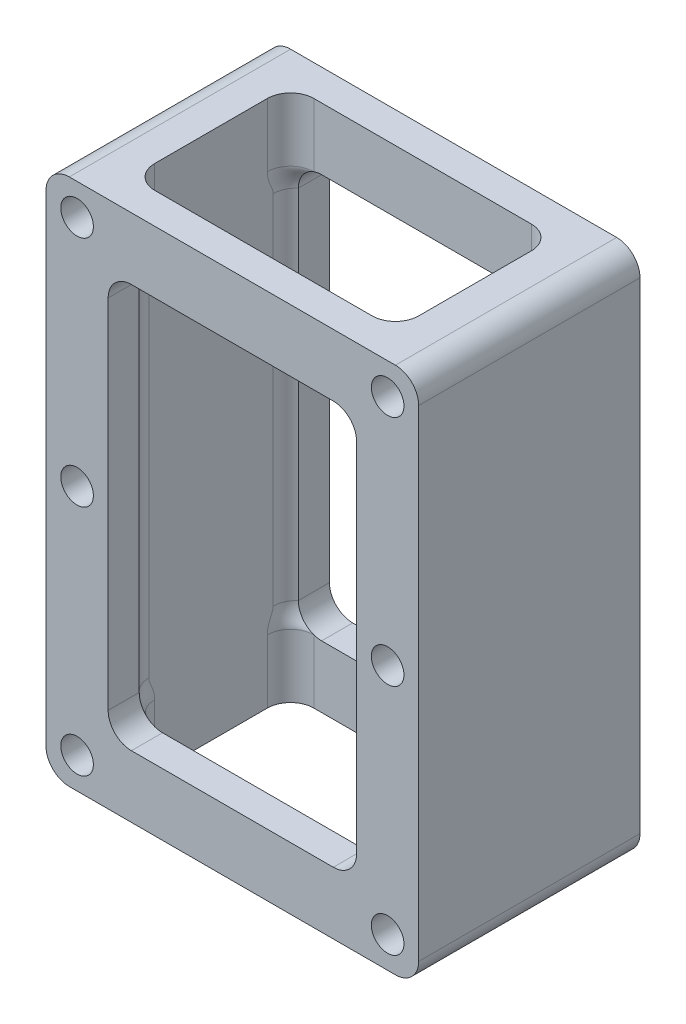
SolidWorks part; units mm, degrees
ref_plane "前视基准面" through (0, 0, 0) normal (0, 0, 1) x (1, 0, 0)
ref_plane "上视基准面" through (0, 0, 0) normal (0, 1, 0) x (1, 0, 0)
ref_plane "右视基准面" through (0, 0, 0) normal (1, 0, 0) x (0, 0, -1)
sketch "草图1" plane through (0, 0, 0) normal (0, 0, 1) x (1, 0, 0)
  line L0 (0, -1000) -> (0, 49000) construction
  line L1 (-24, 34) -> (24, 34)
  line L2 (-24, 34) -> (-24, -34)
  line L3 (-24, -34) -> (24, -34)
  line L4 (24, 34) -> (24, -34)
  line L5 (-24, 34) -> (24, -34) construction
  line L6 (-24, -34) -> (24, 34) construction
  line L7 (-20, 30) -> (20, 30) construction
  line L8 (-20, 30) -> (-20, -30) construction
  line L9 (-20, -30) -> (20, -30) construction
  line L10 (20, 30) -> (20, -30) construction
  line L11 (-20, 30) -> (20, -30) construction
  line L12 (-20, -30) -> (20, 30) construction
  line L13 (-16, 26) -> (16, 26)
  line L14 (16, 26) -> (16, -26)
  line L15 (-16, -26) -> (16, -26)
  line L16 (-16, 26) -> (-16, -26)
  circle A0 centre (-20, 30) radius 2.1
  circle A1 centre (-20, 0) radius 2.1
  circle A2 centre (-20, -30) radius 2.1
  circle A3 centre (20, -30) radius 2.1
  circle A4 centre (20, 0) radius 2.1
  circle A5 centre (20, 30) radius 2.1
  point P0 (0, 0)
  point P6 (0, 0)
  dimension "D5" = 4.2
  dimension "D6" = 4.2
  dimension "D7" = 4.2
  dimension "D1" = 48
  dimension "D2" = 68
  dimension "D3" = 40
  dimension "D4" = 60
  dimension "D8" = 8
extrude "凸台-拉伸1" add sketch "草图1" along normal blind 28.5
fillet "圆角1" radius 3 8 edges at (-24, -34, 14.25) (24, -34, 14.25) (-16, -26, 14.25) (16, -26, 14.25) (16, 26, 14.25) (-16, 26, 14.25) (-24, 34, 14.25) (24, 34, 14.25)
sketch "草图2" plane through (0, -34, 0) normal (0, -1, 0) x (1, 0, 0)
  line L0 (17, 24.5) -> (-17, 24.5)
  line L1 (-17, 24.5) -> (-17, 4)
  line L2 (-17, 4) -> (17, 4)
  line L3 (17, 4) -> (17, 24.5)
  line L4 (21, 28.5) -> (-21, 28.5)
  line L5 (-21, 28.5) -> (-21, 0)
  line L6 (-21, 0) -> (21, 0)
  line L7 (21, 0) -> (21, 28.5)
  line L8 (21, 28.5) -> (-21, 28.5) construction
  line L9 (-21, 28.5) -> (-21, 0)
  line L10 (-21, 0) -> (21, 0)
  line L11 (21, 0) -> (21, 28.5) construction
  dimension "D1" = 0
  dimension "D2" = 4
extrude "切除-拉伸1" cut sketch "草图2" against normal through all contours L2 L3 L0 L1 region at (0, -34, 14.25)
fillet "圆角2" radius 3 4 edges at (-17, 0, 4) (17, 0, 4) (17, 0, 24.5) (-17, 0, 24.5)
